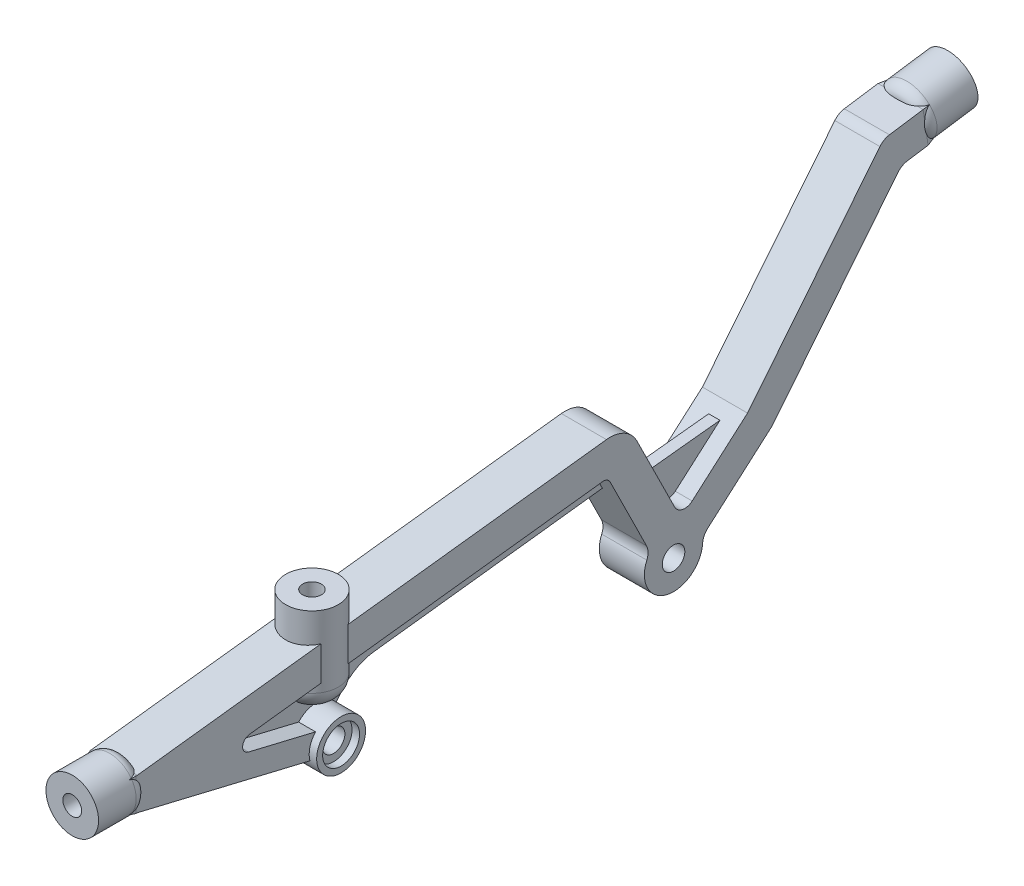
SolidWorks part; units mm, degrees
ref_plane "Front Plane" through (0, 0, 0) normal (0, 0, 1) x (1, 0, 0)
ref_plane "Top Plane" through (0, 0, 0) normal (0, 1, 0) x (1, 0, 0)
ref_plane "Right Plane" through (0, 0, 0) normal (1, 0, 0) x (0, 0, -1)
sketch "Sketch2" plane through (0, 0, 0) normal (1, 0, 0) x (0, 0, -1)
  line L0 (-47.5044, 4.2147) -> (-41.8474, 4.2147)
  line L1 (24.6135, 9.4888) -> (29.629, -0.633)
  line L2 (39.3231, 5.348) -> (31.961, -1.0957)
  line L3 (58.2, 27.9724) -> (69.1154, 29.585)
  line L4 (69.1154, 29.585) -> (69.773, 25.1333)
  line L5 (69.773, 25.1333) -> (60.6019, 23.7784)
  line L6 (59.3356, 23.0532) -> (42.5831, 2.2211)
  line L7 (42.5831, 2.2211) -> (34.0286, -5.2663)
  line L8 (39.3231, 5.348) -> (56.9338, 27.2472)
  line L9 (-26.9587, 1.4648) -> (20.0369, 7.0904)
  line L10 (21.0518, 6.5415) -> (25.8825, -3.2073)
  line L11 (-27.0727, -0.5006) -> (-18.1436, -2.6383)
  line L12 (-41.8474, -0.1083) -> (-18.897, -5.6029)
  line L13 (-47.5044, 4.2147) -> (-47.5044, -0.1083)
  line L14 (-41.8474, -0.1083) -> (-47.5044, -0.1083)
  line L15 (-41.8474, 4.2147) -> (20.554, 11.6844)
  line L16 (-47.5044, 2.0532) -> (-15.7409, -4.8269) construction
  arc A0 (33.3491, -6.6559) -> (25.9254, -4.8909) centre (29.4806, -6.4324) cw
  circle A1 centre (-15.7409, -4.8269) radius 3.25
  arc A2 (-26.9587, 1.4648) -> (-27.0727, -0.5006) centre (-26.8399, 0.4719) ccw
  arc A3 (24.6135, 9.4888) -> (20.554, 11.6844) centre (21.0294, 7.7128) ccw
  arc A4 (21.0518, 6.5415) -> (20.0369, 7.0904) centre (20.1557, 6.0975) ccw
  arc A5 (33.3491, -6.6559) -> (34.0286, -5.2663) centre (35.3458, -6.7712) cw
  arc A6 (25.9254, -4.8909) -> (25.8825, -3.2073) centre (24.0904, -4.0953) ccw
  arc A7 (31.961, -1.0957) -> (29.629, -0.633) centre (30.9731, 0.033) cw
  arc A8 (59.3356, 23.0532) -> (60.6019, 23.7784) centre (60.8942, 21.7998) cw
  arc A9 (56.9338, 27.2472) -> (58.2, 27.9724) centre (58.4923, 25.9938) cw
  circle A10 centre (-15.7409, -4.8269) radius 1.5
  circle A11 centre (29.4806, -6.4324) radius 1.5
  dimension "D2" = 6.5
  dimension "D3" = 3.875
  dimension "D16" = 1
  dimension "D17" = 4
  dimension "D18" = 1
  dimension "D19" = 2
  dimension "D20" = 1.5
  dimension "D21" = 2
  dimension "D22" = 3
  dimension "D23" = 3
  dimension "D4" = 4.5
  dimension "D5" = 109.533
  dimension "D6" = 45.25
  dimension "D7" = 32.5
  dimension "D8" = 4.8269
  dimension "D9" = 15.7409
  dimension "D10" = 47.5044
  dimension "D11" = 4.5
  dimension "D12" = 4.323
  dimension "D13" = 4.5
  dimension "D14" = 4.5
  dimension "D15" = 4.5
extrude "Boss-Extrude3" add sketch "Sketch2" along normal blind 3 and the other way blind 3 separate body contours L13 L16 A1 L11 A2 L9 A4 L10 A6 A0 A5 L7 L6 A8 L5 L4 L3 A9 L8 L2 A7 L1 A3 L15 L0 | L16 L13 L14 L12 A1 | A1 region at (0, 7.1495, -14.4665) region at (0, -1.6766, 33.3239) region at (0, -3.3796, 18.5479)
chamfer "Chamfer1" distance 5.5 angle 10 4 edges at (0, 4.2147, 47.5044) (3, 2.0532, 47.5044) (0, -0.1083, 47.5044) (-3, 2.0532, 47.5044) first distance on face at (0, 4.2147, 44.6759) first distance on face at (3, 6.6533, -17.5926) first distance on face at (0, -0.1083, 44.6759) first distance on face at (-3, 6.6533, -17.5926)
sketch "Sketch4" plane through (0, 0, 47.5044) normal (0, 0, 1) x (1, 0, 0)
  line L0 (2.0302, 2.0532) -> (0, 2.0602) construction
  line L1 (2.0302, 0.8615) -> (2.0302, 3.2449) construction
  line L2 (0, 0.8615) -> (0, 1.1013) construction
  line L3 (-2.0302, 0.8615) -> (2.0302, 0.8615) construction
  circle A0 centre (0, 2.0602) radius 3.5
  dimension "D1" = 7
extrude "Boss-Extrude5" add sketch "Sketch4" against normal blind 6.5
fillet "Fillet1" radius 1.5 4 edges at (-3.5, 2.0602, 41.0044) (0, -1.4398, 41.0044) (3.5, 2.0602, 41.0044) (0, 5.5602, 41.0044)
chamfer "Chamfer2" distance 6.5 angle 10 4 edges at (-3, 27.3591, -69.4442) (0, 29.585, -69.1154) (0, 25.1333, -69.773) (3, 27.3591, -69.4442) first distance on face at (-3, 6.3365, -13.75) first distance on face at (0, 28.7787, -63.6577) first distance on face at (0, 24.4558, -65.1875) first distance on face at (3, 6.3452, -13.7488)
sketch "Sketch5" plane through (0, 10.6247, -71.9165) normal (0, 0.1462, -0.9893) x (-1, 0, 0)
  line L0 (0, 18.0199) -> (0, 17.6456) construction
  line L1 (1.8539, 18.0199) -> (-1.8539, 18.0199) construction
  line L2 (-1.8539, 16.9161) -> (-4.264, 16.9161) construction
  line L3 (-1.8539, 18.0199) -> (-1.8539, 15.8122) construction
  circle A0 centre (0, 16.9161) radius 3.5
  dimension "D1" = 7
extrude "Boss-Extrude6" add sketch "Sketch5" against normal blind 7
fillet "Fillet2" radius 1.5 4 edges at (-3.5, 26.3361, -62.5194) (0, 29.7985, -62.0078) (3.5, 26.3361, -62.5194) (0, 22.8737, -63.0309)
sketch "Sketch6" plane through (0, 0, 47.5044) normal (0, 0, 1) x (1, 0, 0)
  circle A0 centre (0, 2.0602) radius 1.25
  circle A1 centre (0, 2.0602) radius 3.5 construction
  dimension "D1" = 2.5
extrude "Cut-Extrude1" cut sketch "Sketch6" against normal blind 5
sketch "Sketch7" plane through (0, 10.6247, -71.9165) normal (0, 0.1462, -0.9893) x (-1, 0, 0)
  circle A0 centre (0, 16.9161) radius 1.25
  dimension "D1" = 2.5
extrude "Cut-Extrude2" cut sketch "Sketch7" against normal blind 5
sketch "Sketch8" plane through (3, 0, 0) normal (1, 0, 0) x (0, 0, -1)
  circle A0 centre (-15.7409, -4.8269) radius 2.4563
  circle A1 centre (-15.7409, -4.8269) radius 3.25
  arc A3 (-18.897, -5.6029) -> (-18.1436, -2.6383) centre (-15.7409, -4.8269) ccw construction
  dimension "D1" = 0.7937
extrude "Boss-Extrude7" add sketch "Sketch8" along normal blind 1
mirror "Mirror1" about plane through (0, 0, 0) normal (1, 0, 0) of "Boss-Extrude7"
ref_plane "Plane2" through (0, 11, 0) normal (0, 1, 0) x (1, 0, 0)
sketch "Sketch9" plane through (0, 11, 0) normal (0, 1, 0) x (1, 0, 0)
  line L0 (0, 0) -> (0, -2.2376) construction
  circle A0 centre (0, -15.6173) radius 3.5
  dimension "D1" = 7
extrude "Boss-Extrude8" add sketch "Sketch9" against normal blind 12
fillet "Fillet4" radius 2.5 1 edges at (0, -1, 19.1173)
sketch "Sketch10" plane through (0, 11, 0) normal (0, 1, 0) x (1, 0, 0)
  circle A0 centre (0, -15.6173) radius 1.25
  circle A1 centre (0, -15.6173) radius 3.5 construction
  dimension "D1" = 2.5
extrude "Cut-Extrude3" cut sketch "Sketch10" against normal blind 7.5
sketch "Sketch11" plane through (0, 0, 0) normal (1, 0, 0) x (0, 0, -1)
  line L30 (-27.0727, -0.5006) -> (-18.1436, -2.6383)
  line L31 (-17.42, 2.6066) -> (-26.9587, 1.4648)
  line L32 (-27.0727, -0.5006) -> (-18.1436, -2.6383)
  line L33 (-17.42, 2.6066) -> (-26.9587, 1.4648)
  line L36 (22.2596, 4.104) -> (-8.0885, 0.4719)
  line L38 (21.0518, 6.5415) -> (25.8825, -3.2073)
  line L39 (-13.8145, 3.0382) -> (20.0369, 7.0904)
  line L40 (21.0518, 6.5415) -> (25.8825, -3.2073)
  line L41 (-13.8145, 3.0382) -> (20.0369, 7.0904)
  line L47 (39.3231, 5.348) -> (31.961, -1.0957) construction
  line L53 (-62.9167, 46.5625) -> (-62.9167, -39.8958)
  line L54 (-62.9167, -39.8958) -> (77.0833, -39.8958)
  line L55 (77.0833, -39.8958) -> (77.0833, 46.5625)
  line L56 (77.0833, 46.5625) -> (-62.9167, 46.5625)
  line L57 (27.8151, 3.0277) -> (37.9018, 4.104)
  line L62 (-17.42, 2.6066) -> (-13.8145, 3.0382)
  line L64 (39.3231, 5.348) -> (31.961, -1.0957)
  line L65 (29.629, -0.633) -> (24.6135, 9.4888)
  line L66 (39.3231, 5.348) -> (31.961, -1.0957)
  line L67 (29.629, -0.633) -> (24.6135, 9.4888)
  arc A21 (-26.9587, 1.4648) -> (-27.0727, -0.5006) centre (-26.8399, 0.4719) ccw
  arc A22 (-26.9587, 1.4648) -> (-27.0727, -0.5006) centre (-26.8399, 0.4719) ccw
  circle A24 centre (-15.7409, -4.8269) radius 3.25
  arc A25 (21.0518, 6.5415) -> (20.0369, 7.0904) centre (20.1557, 6.0975) ccw
  arc A26 (21.0518, 6.5415) -> (20.0369, 7.0904) centre (20.1557, 6.0975) ccw
  circle A27 centre (-15.7409, -4.8269) radius 3.25 construction
  arc A33 (29.629, -0.633) -> (31.961, -1.0957) centre (30.9731, 0.033) ccw
  arc A34 (29.629, -0.633) -> (31.961, -1.0957) centre (30.9731, 0.033) ccw
  spline S0 degree 2 poles (-8.0885, 0.4719) (-11.0981, 0.1117) (-13.148, -2.8675) knots 0 0 0 1 1 1
  dimension "D1" = 0
  dimension "D2" = 0
  dimension "D4" = 0
extrude "Boss-Extrude9" add sketch "Sketch11" along normal blind 0.75 and the other way blind 0.75 contours S0 L36 L40 A26 L41 L62 L33 A22 L32 A24 | L67 A34 L66 L57 region at (0, 2.3805, 3.909) region at (0, 1.6853, -32.115)
ref_axis "Axis1" through (0, 26.644, -64.6035) along (0, 0.1462, -0.9893)
ref_plane "Plane3" through (0, 16.7344, 2.4723) normal (0, -0.9893, -0.1462) x (0, 0.1462, -0.9893)
